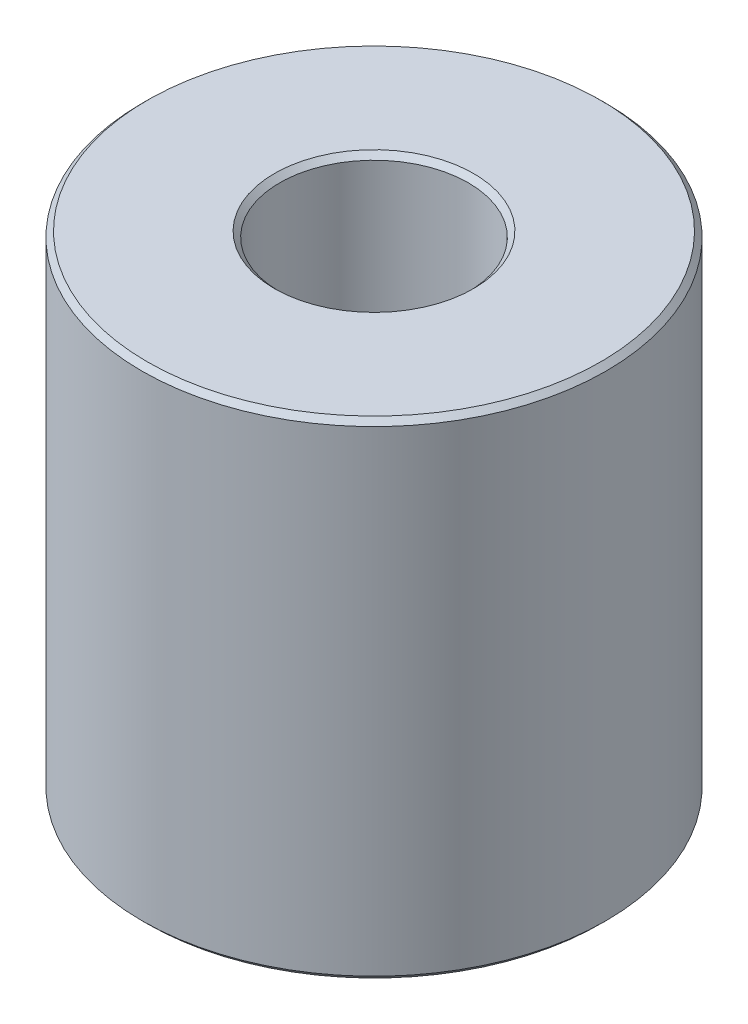
SolidWorks part; units mm, degrees
ref_plane "Front Plane" through (0, 0, 0) normal (0, 0, 1) x (1, 0, 0)
ref_plane "Top Plane" through (0, 0, 0) normal (0, 1, 0) x (1, 0, 0)
ref_plane "Right Plane" through (0, 0, 0) normal (1, 0, 0) x (0, 0, -1)
sketch "Sketch1" plane through (0, 0, 0) normal (0, 1, 0) x (1, 0, 0)
  circle A0 centre (0, 0) radius 55
  dimension "SLEEVE_OD" = 110
extrude "Boss-Extrude1" add sketch "Sketch1" along normal blind 115.3847
sketch "Sketch2" plane through (0, 0, 0) normal (0, 1, 0) x (1, 0, 0)
  circle A0 centre (0, 0) radius 22.3645
  dimension "BORE_D" = 44.729
extrude "Cut-Extrude1" cut sketch "Sketch2" along normal through all
chamfer "Chamfer1" distance 1.2672 angle 45 4 edges at (0, 115.3847, 22.3645) (0, 0, 22.3645) (0, 0, 55) (0, 115.3847, 55)
